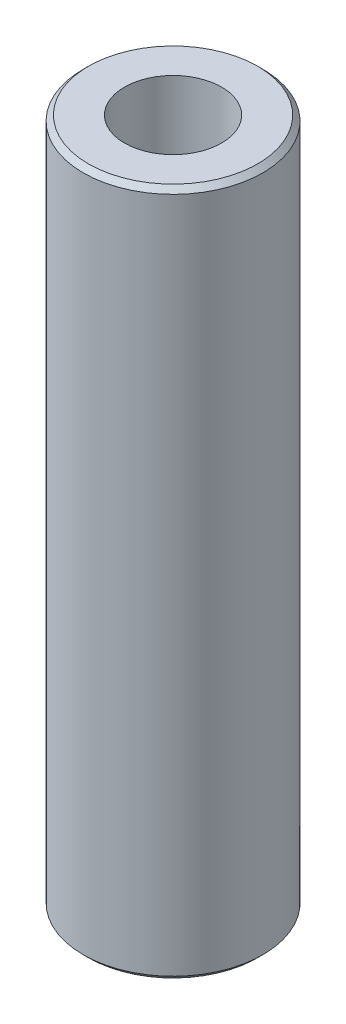
SolidWorks part; units mm, degrees
ref_plane "Front Plane" through (0, 0, 0) normal (0, 0, 1) x (1, 0, 0)
ref_plane "Top Plane" through (0, 0, 0) normal (0, 1, 0) x (1, 0, 0)
ref_plane "Right Plane" through (0, 0, 0) normal (1, 0, 0) x (0, 0, -1)
sketch "Sketch1" plane through (0, 0, 0) normal (0, 1, 0) x (1, 0, 0)
  circle A0 centre (0, 0) radius 37.5
  dimension "SHAFT_OD" = 75
extrude "Boss-Extrude1" add sketch "Sketch1" along normal blind 287.0961
sketch "Sketch2" plane through (0, 0, 0) normal (0, 1, 0) x (1, 0, 0)
  circle A0 centre (0, 0) radius 20.2681
  dimension "BORE_D" = 40.5362
extrude "Cut-Extrude1" cut sketch "Sketch2" along normal through all
chamfer "Chamfer1" distance 2.1658 angle 45 2 edges at (0, 287.0961, 37.5) (0, 0, 37.5)
